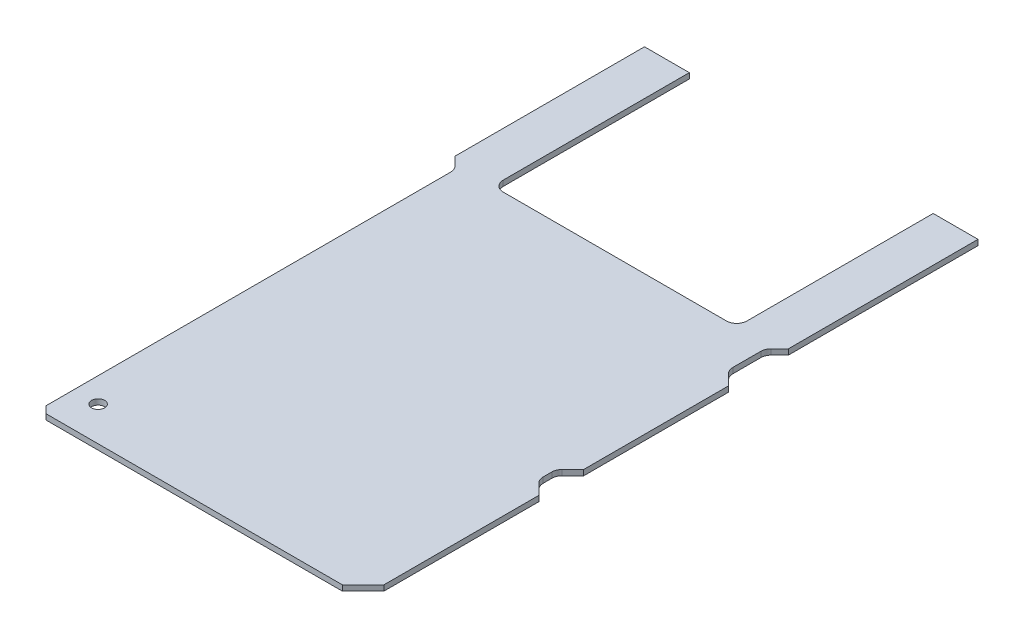
SolidWorks part; units mm, degrees
ref_plane "Front Plane" through (0, 0, 0) normal (0, 0, 1) x (1, 0, 0)
ref_plane "Top Plane" through (0, 0, 0) normal (0, 1, 0) x (1, 0, 0)
ref_plane "Right Plane" through (0, 0, 0) normal (1, 0, 0) x (0, 0, -1)
sketch "Sketch1" plane through (0, 0, 0) normal (0, 1, 0) x (1, 0, 0)
  line L1 (45, -88.5) -> (-45, -88.5)
  line L2 (45, -88.5) -> (45, 88.5)
  line L3 (45, 88.5) -> (-45, 88.5)
  line L4 (-45, -88.5) -> (-45, 88.5)
  line L5 (45, -88.5) -> (-45, 88.5) construction
  line L6 (45, 88.5) -> (-45, -88.5) construction
  point P0 (0, 0)
  dimension "D1" = 90
  dimension "D2" = 177
extrude "Boss-Extrude1" add sketch "Sketch1" along normal blind 1.6
sketch "Sketch5" plane through (0, 0, 0) normal (0, -1, 0) x (1, 0, 0)
  line L0 (45, 88.5) -> (45, -88.5) construction
  line L1 (37.6, -44) -> (37.6, -48)
  line L2 (37.6, -44) -> (22.4, -44)
  line L3 (22.4, -44) -> (22.4, -48)
  line L4 (37.6, -48) -> (22.4, -48)
  line L5 (16.1, -44) -> (16.1, -48)
  line L6 (16.1, -44) -> (0.9, -44)
  line L7 (0.9, -44) -> (0.9, -48)
  line L8 (16.1, -48) -> (0.9, -48)
  line L9 (37.6, -80) -> (37.6, -84)
  line L10 (37.6, -80) -> (22.4, -80)
  line L11 (22.4, -80) -> (22.4, -84)
  line L12 (37.6, -84) -> (22.4, -84)
  line L13 (12.1, -80) -> (12.1, -84)
  line L14 (12.1, -80) -> (-3.1, -80)
  line L15 (-3.1, -80) -> (-3.1, -84)
  line L16 (12.1, -84) -> (-3.1, -84)
  line L17 (2.025, -44.54) -> (14.975, -44.54)
  line L18 (2.025, -44.54) -> (2.025, -47.46)
  line L19 (2.025, -47.46) -> (14.975, -47.46)
  line L20 (14.975, -44.54) -> (14.975, -47.46)
  line L21 (23.525, -44.54) -> (36.475, -44.54)
  line L22 (23.525, -44.54) -> (23.525, -47.46)
  line L23 (23.525, -47.46) -> (36.475, -47.46)
  line L24 (36.475, -44.54) -> (36.475, -47.46)
  line L25 (-1.975, -80.54) -> (10.975, -80.54)
  line L26 (-1.975, -80.54) -> (-1.975, -83.46)
  line L27 (-1.975, -83.46) -> (10.975, -83.46)
  line L28 (10.975, -80.54) -> (10.975, -83.46)
  line L29 (23.525, -80.54) -> (36.475, -80.54)
  line L30 (23.525, -80.54) -> (23.525, -83.46)
  line L31 (23.525, -83.46) -> (36.475, -83.46)
  line L32 (36.475, -80.54) -> (36.475, -83.46)
  line L33 (-22, -41.5) -> (43, -41.5) construction
  line L34 (-22, -41.5) -> (-22, -86.5) construction
  line L35 (-22, -86.5) -> (43, -86.5) construction
  line L36 (43, -41.5) -> (43, -86.5) construction
  line L37 (45, -88.5) -> (-45, -88.5) construction
  point P16 (8.5, -44)
  point P17 (30, -44)
  point P18 (4.5, -84)
  point P19 (30, -84)
  point P25 (37.6, -82)
  point P26 (37.6, -46)
  point P38 (8.5, -44.54)
  point P39 (2.025, -46)
  point P40 (0.9, -46)
  point P41 (30, -44.54)
  point P42 (-1.975, -82)
  point P43 (-3.1, -82)
  point P44 (4.5, -83.46)
  point P45 (30, -83.46)
  dimension "D1" = 15.2
  dimension "D2" = 4
  dimension "D3" = 21.5
  dimension "D4" = 25.5
  dimension "D5" = 2.92
  dimension "D6" = 12.95
  dimension "D7" = 36
  dimension "D8" = 65
  dimension "D9" = 45
  dimension "D10" = 2.5
  dimension "D11" = 5.4
  dimension "D12" = 2
  dimension "D13" = 2
sketch "Sketch7" plane through (0, 0, 0) normal (0, -1, 0) x (1, 0, 0)
  line L0 (-45, -30.1257) -> (-48.3743, -33.5)
  line L1 (-45, -88.5) -> (-48.3743, -88.5)
  line L2 (-45, -88.5) -> (-45, -30.1257)
  line L4 (-48.3743, -88.5) -> (-48.3743, -33.5)
  line L5 (45, -88.5) -> (48.3743, -88.5)
  line L6 (45, -88.5) -> (45, -30.1257)
  line L8 (48.3743, -88.5) -> (48.3743, -33.5)
  line L9 (45, -30.1257) -> (48.3743, -33.5)
  line M9 (-45, 88.5) -> (-45, -88.5)
  line M11 (45, -88.5) -> (45, 88.5)
  dimension "D1" = 3.3743
  dimension "D2" = 55
  dimension "D3" = 45
extrude "Boss-Extrude4" add sketch "Sketch7" against normal up to surface (1.6 mm away) contours L4 L1 L0 M9 | L9 L5 L8 M11 region at (-46.6704, 0, -60.1481) region at (46.6704, 0, -60.1481) up to face at (0, 1.6, 0)
sketch "Sketch8" plane through (0, 1.6, 0) normal (0, 1, 0) x (1, 0, 0)
  line L0 (-30.48, 25.5) -> (30.48, 25.5) construction
  line L2 (48.3743, 88.5) -> (-48.3743, 88.5) construction
  line L3 (31.0783, -41.8002) -> (31.0783, -43.6252) construction
  line L4 (31.0783, -43.6252) -> (29.8783, -43.6252) construction
  line L5 (31.0783, -79.9002) -> (31.0783, -81.7252) construction
  line L6 (31.0783, -81.7252) -> (29.8783, -81.7252) construction
  line L7 (6.9977, -30.7614) -> (6.9977, -16.766)
  line L8 (6.9977, -16.766) -> (-6.9977, -16.766)
  line L9 (-6.9977, -16.766) -> (-6.9977, -30.7614)
  line L10 (-6.9977, -30.7614) -> (6.9977, -30.7614)
  line L11 (6.9977, -30.7614) -> (6.9977, -16.766)
  line L12 (6.9977, -16.766) -> (-6.9977, -16.766)
  line L13 (-6.9977, -16.766) -> (-6.9977, -30.7614)
  line L14 (-6.9977, -30.7614) -> (6.9977, -30.7614)
  line L15 (-11.9253, -30.7614) -> (-11.9253, -16.766)
  line L16 (-11.9253, -16.766) -> (-25.9207, -16.766)
  line L17 (-25.9207, -16.766) -> (-25.9207, -30.7614)
  line L18 (-25.9207, -30.7614) -> (-11.9253, -30.7614)
  line L19 (-11.9253, -30.7614) -> (-11.9253, -16.766)
  line L20 (-11.9253, -16.766) -> (-25.9207, -16.766)
  line L21 (-25.9207, -16.766) -> (-25.9207, -30.7614)
  line L22 (-25.9207, -30.7614) -> (-11.9253, -30.7614)
  line L23 (44.8437, -11.8384) -> (44.8437, 2.157)
  line L24 (44.8437, 2.157) -> (30.8483, 2.157)
  line L25 (30.8483, 2.157) -> (30.8483, -11.8384)
  line L26 (30.8483, -11.8384) -> (44.8437, -11.8384)
  line L27 (44.8437, -11.8384) -> (44.8437, 2.157)
  line L28 (44.8437, 2.157) -> (30.8483, 2.157)
  line L29 (30.8483, 2.157) -> (30.8483, -11.8384)
  line L30 (30.8483, -11.8384) -> (44.8437, -11.8384)
  line L31 (6.9977, -49.6844) -> (6.9977, -35.689)
  line L32 (6.9977, -35.689) -> (-6.9977, -35.689)
  line L33 (-6.9977, -35.689) -> (-6.9977, -49.6844)
  line L34 (-6.9977, -49.6844) -> (6.9977, -49.6844)
  line L35 (6.9977, -49.6844) -> (6.9977, -35.689)
  line L36 (6.9977, -35.689) -> (-6.9977, -35.689)
  line L37 (-6.9977, -35.689) -> (-6.9977, -49.6844)
  line L38 (-6.9977, -49.6844) -> (6.9977, -49.6844)
  line L39 (-11.9253, -49.6844) -> (-11.9253, -35.689)
  line L40 (-11.9253, -35.689) -> (-25.9207, -35.689)
  line L41 (-25.9207, -35.689) -> (-25.9207, -49.6844)
  line L42 (-25.9207, -49.6844) -> (-11.9253, -49.6844)
  line L43 (-11.9253, -49.6844) -> (-11.9253, -35.689)
  line L44 (-11.9253, -35.689) -> (-25.9207, -35.689)
  line L45 (-25.9207, -35.689) -> (-25.9207, -49.6844)
  line L46 (-25.9207, -49.6844) -> (-11.9253, -49.6844)
  line L47 (25.9207, -30.7614) -> (25.9207, -16.766)
  line L48 (25.9207, -16.766) -> (11.9253, -16.766)
  line L49 (11.9253, -16.766) -> (11.9253, -30.7614)
  line L50 (11.9253, -30.7614) -> (25.9207, -30.7614)
  line L51 (25.9207, -30.7614) -> (25.9207, -16.766)
  line L52 (25.9207, -16.766) -> (11.9253, -16.766)
  line L53 (11.9253, -16.766) -> (11.9253, -30.7614)
  line L54 (11.9253, -30.7614) -> (25.9207, -30.7614)
  line L55 (6.9977, -68.6074) -> (6.9977, -54.612)
  line L56 (6.9977, -54.612) -> (-6.9977, -54.612)
  line L57 (-6.9977, -54.612) -> (-6.9977, -68.6074)
  line L58 (-6.9977, -68.6074) -> (6.9977, -68.6074)
  line L59 (6.9977, -68.6074) -> (6.9977, -54.612)
  line L60 (6.9977, -54.612) -> (-6.9977, -54.612)
  line L61 (-6.9977, -54.612) -> (-6.9977, -68.6074)
  line L62 (-6.9977, -68.6074) -> (6.9977, -68.6074)
  line L63 (-11.9253, -68.6074) -> (-11.9253, -54.612)
  line L64 (-11.9253, -54.612) -> (-25.9207, -54.612)
  line L65 (-25.9207, -54.612) -> (-25.9207, -68.6074)
  line L66 (-25.9207, -68.6074) -> (-11.9253, -68.6074)
  line L67 (-11.9253, -68.6074) -> (-11.9253, -54.612)
  line L68 (-11.9253, -54.612) -> (-25.9207, -54.612)
  line L69 (-25.9207, -54.612) -> (-25.9207, -68.6074)
  line L70 (-25.9207, -68.6074) -> (-11.9253, -68.6074)
  line L71 (25.9207, -49.6844) -> (25.9207, -35.689)
  line L72 (25.9207, -35.689) -> (11.9253, -35.689)
  line L73 (11.9253, -35.689) -> (11.9253, -49.6844)
  line L74 (11.9253, -49.6844) -> (25.9207, -49.6844)
  line L75 (25.9207, -49.6844) -> (25.9207, -35.689)
  line L76 (25.9207, -35.689) -> (11.9253, -35.689)
  line L77 (11.9253, -35.689) -> (11.9253, -49.6844)
  line L78 (11.9253, -49.6844) -> (25.9207, -49.6844)
  line L79 (25.9207, -68.6074) -> (25.9207, -54.612)
  line L80 (25.9207, -54.612) -> (11.9253, -54.612)
  line L81 (11.9253, -54.612) -> (11.9253, -68.6074)
  line L82 (11.9253, -68.6074) -> (25.9207, -68.6074)
  line L83 (25.9207, -68.6074) -> (25.9207, -54.612)
  line L84 (25.9207, -54.612) -> (11.9253, -54.612)
  line L85 (11.9253, -54.612) -> (11.9253, -68.6074)
  line L86 (11.9253, -68.6074) -> (25.9207, -68.6074)
  line L87 (-30.8483, -30.7614) -> (-30.8483, -16.766)
  line L88 (-30.8483, -16.766) -> (-44.8437, -16.766)
  line L89 (-44.8437, -16.766) -> (-44.8437, -30.7614)
  line L90 (-44.8437, -30.7614) -> (-30.8483, -30.7614)
  line L91 (-30.8483, -30.7614) -> (-30.8483, -16.766)
  line L92 (-30.8483, -16.766) -> (-44.8437, -16.766)
  line L93 (-44.8437, -16.766) -> (-44.8437, -30.7614)
  line L94 (-44.8437, -30.7614) -> (-30.8483, -30.7614)
  line L95 (-30.8483, -11.8384) -> (-30.8483, 2.157)
  line L96 (-30.8483, 2.157) -> (-44.8437, 2.157)
  line L97 (-44.8437, 2.157) -> (-44.8437, -11.8384)
  line L98 (-44.8437, -11.8384) -> (-30.8483, -11.8384)
  line L99 (-30.8483, -11.8384) -> (-30.8483, 2.157)
  line L100 (-30.8483, 2.157) -> (-44.8437, 2.157)
  line L101 (-44.8437, 2.157) -> (-44.8437, -11.8384)
  line L102 (-44.8437, -11.8384) -> (-30.8483, -11.8384)
  line L103 (25.9207, -87.5304) -> (25.9207, -73.535)
  line L104 (25.9207, -73.535) -> (11.9253, -73.535)
  line L105 (11.9253, -73.535) -> (11.9253, -87.5304)
  line L106 (11.9253, -87.5304) -> (25.9207, -87.5304)
  line L107 (25.9207, -87.5304) -> (25.9207, -73.535)
  line L108 (25.9207, -73.535) -> (11.9253, -73.535)
  line L109 (11.9253, -73.535) -> (11.9253, -87.5304)
  line L110 (11.9253, -87.5304) -> (25.9207, -87.5304)
  line L111 (-30.8483, -87.5304) -> (-30.8483, -73.535)
  line L112 (-30.8483, -73.535) -> (-44.8437, -73.535)
  line L113 (-44.8437, -73.535) -> (-44.8437, -87.5304)
  line L114 (-44.8437, -87.5304) -> (-30.8483, -87.5304)
  line L115 (-30.8483, -87.5304) -> (-30.8483, -73.535)
  line L116 (-30.8483, -73.535) -> (-44.8437, -73.535)
  line L117 (-44.8437, -73.535) -> (-44.8437, -87.5304)
  line L118 (-44.8437, -87.5304) -> (-30.8483, -87.5304)
  line L119 (-30.8483, -68.6074) -> (-30.8483, -54.612)
  line L120 (-30.8483, -54.612) -> (-44.8437, -54.612)
  line L121 (-44.8437, -54.612) -> (-44.8437, -68.6074)
  line L122 (-44.8437, -68.6074) -> (-30.8483, -68.6074)
  line L123 (-30.8483, -68.6074) -> (-30.8483, -54.612)
  line L124 (-30.8483, -54.612) -> (-44.8437, -54.612)
  line L125 (-44.8437, -54.612) -> (-44.8437, -68.6074)
  line L126 (-44.8437, -68.6074) -> (-30.8483, -68.6074)
  line L127 (-30.8483, -49.6844) -> (-30.8483, -35.689)
  line L128 (-30.8483, -35.689) -> (-44.8437, -35.689)
  line L129 (-44.8437, -35.689) -> (-44.8437, -49.6844)
  line L130 (-44.8437, -49.6844) -> (-30.8483, -49.6844)
  line L131 (-30.8483, -49.6844) -> (-30.8483, -35.689)
  line L132 (-30.8483, -35.689) -> (-44.8437, -35.689)
  line L133 (-44.8437, -35.689) -> (-44.8437, -49.6844)
  line L134 (-44.8437, -49.6844) -> (-30.8483, -49.6844)
  line L135 (45.0596, 90.786) -> (-45.0596, 90.786)
  line L136 (-45.0596, 90.786) -> (-45.0596, 30.08)
  line L137 (-45.0596, 30.08) -> (45.0596, 30.08)
  line L138 (45.0596, 30.08) -> (45.0596, 90.786)
  line L139 (45.0596, 90.786) -> (-45.0596, 90.786)
  line L140 (-45.0596, 90.786) -> (-45.0596, 30.08)
  line L141 (-45.0596, 30.08) -> (45.0596, 30.08)
  line L142 (45.0596, 30.08) -> (45.0596, 90.786)
  line L143 (52.5, 98.836) -> (-52.5, 98.836)
  line L144 (52.5, -92.8744) -> (52.5, 98.836)
  line L145 (-52.5, -92.8744) -> (52.5, -92.8744)
  line L146 (-52.5, 98.836) -> (-52.5, -92.8744)
  line L147 (52.5, 98.836) -> (-52.5, 98.836)
  line L148 (52.5, -92.8744) -> (52.5, 98.836)
  line L149 (-52.5, -92.8744) -> (52.5, -92.8744)
  line L150 (-52.5, 98.836) -> (-52.5, -92.8744)
  line L151 (-18.0365, -73.765) -> (-19.8615, -73.765) construction
  line L152 (-19.8615, -73.765) -> (-19.8615, -72.565) construction
  line L153 (31.8783, -41.8002) -> (31.0783, -41.8002) construction
  line L154 (31.8783, -79.9002) -> (31.0783, -79.9002) construction
  line L155 (-18.0365, -74.565) -> (-18.0365, -73.765) construction
  line L156 (31.8783, -40.2252) -> (31.8783, -41.8002) construction
  line L157 (31.8783, -78.3252) -> (31.8783, -79.9002) construction
  line L158 (-16.4615, -74.565) -> (-18.0365, -74.565) construction
  line L159 (-6.9977, 7.0846) -> (-6.9977, 21.08) construction
  line L160 (6.9977, 21.08) -> (-6.9977, 21.08) construction
  line L161 (31.0783, -48.4502) -> (37.3483, -48.4502) construction
  line L162 (37.3483, -48.4502) -> (40.1483, -48.4502) construction
  line L163 (31.0783, -86.5502) -> (37.3483, -86.5502) construction
  line L164 (37.3483, -86.5502) -> (40.1483, -86.5502) construction
  line L165 (-24.6865, -73.765) -> (-24.6865, -80.035) construction
  line L166 (-24.6865, -80.035) -> (-24.6865, -82.835) construction
  line L167 (6.9977, 7.0846) -> (-6.9977, 7.0846) construction
  line L168 (43.3783, -48.4502) -> (43.3783, -41.8002) construction
  line L169 (43.3783, -41.8002) -> (42.5783, -41.8002) construction
  line L170 (43.3783, -86.5502) -> (43.3783, -79.9002) construction
  line L171 (43.3783, -79.9002) -> (42.5783, -79.9002) construction
  line L172 (-24.6865, -86.065) -> (-18.0365, -86.065) construction
  line L173 (-18.0365, -86.065) -> (-18.0365, -85.265) construction
  line L174 (6.9977, 7.0846) -> (6.9977, 21.08) construction
  line L175 (40.1483, -48.4502) -> (43.3783, -48.4502) construction
  line L176 (40.1483, -86.5502) -> (43.3783, -86.5502) construction
  line L177 (-24.6865, -82.835) -> (-24.6865, -86.065) construction
  line L178 (-25.9207, 7.0846) -> (-25.9207, 21.08) construction
  line L179 (-11.9253, 21.08) -> (-25.9207, 21.08) construction
  line L180 (29.8783, -43.6252) -> (29.8783, -46.6252) construction
  line L181 (29.8783, -81.7252) -> (29.8783, -84.7252) construction
  line L182 (-19.8615, -72.565) -> (-22.8615, -72.565) construction
  line L183 (-11.9253, 7.0846) -> (-25.9207, 7.0846) construction
  line L184 (31.0783, -46.6252) -> (31.0783, -48.4502) construction
  line L185 (31.0783, -84.7252) -> (31.0783, -86.5502) construction
  line L186 (-22.8615, -73.765) -> (-24.6865, -73.765) construction
  line L187 (-30.8483, 7.0846) -> (-44.8437, 7.0846) construction
  line L188 (-30.8483, 7.0846) -> (-30.8483, 21.08) construction
  line L189 (-30.8483, 21.08) -> (-44.8437, 21.08) construction
  line L190 (-44.8437, 7.0846) -> (-44.8437, 21.08) construction
  line L191 (30.8483, -26.2252) -> (30.8483, -40.2252) construction
  line L192 (30.8483, -40.2252) -> (31.8783, -40.2252) construction
  line L193 (30.8483, -64.3252) -> (30.8483, -78.3252) construction
  line L194 (30.8483, -78.3252) -> (31.8783, -78.3252) construction
  line L195 (-2.4615, -73.535) -> (-16.4615, -73.535) construction
  line L196 (-16.4615, -73.535) -> (-16.4615, -74.565) construction
  line L197 (-11.9253, 7.0846) -> (-11.9253, 21.08) construction
  line L198 (29.8783, -46.6252) -> (31.0783, -46.6252) construction
  line L199 (29.8783, -84.7252) -> (31.0783, -84.7252) construction
  line L200 (-22.8615, -72.565) -> (-22.8615, -73.765) construction
  line L201 (-6.9977, -11.8384) -> (-6.9977, 2.157) construction
  line L202 (6.9977, 2.157) -> (-6.9977, 2.157) construction
  line L203 (31.0783, -19.8252) -> (31.0783, -18.0002) construction
  line L204 (29.8783, -19.8252) -> (31.0783, -19.8252) construction
  line L205 (31.0783, -57.9252) -> (31.0783, -56.1002) construction
  line L206 (29.8783, -57.9252) -> (31.0783, -57.9252) construction
  line L207 (3.9385, -73.765) -> (5.7635, -73.765) construction
  line L208 (3.9385, -72.565) -> (3.9385, -73.765) construction
  line L209 (6.9977, -11.8384) -> (-6.9977, -11.8384) construction
  line L210 (31.0783, -22.8252) -> (29.8783, -22.8252) construction
  line L211 (31.0783, -24.6502) -> (31.0783, -22.8252) construction
  line L212 (31.0783, -60.9252) -> (29.8783, -60.9252) construction
  line L213 (31.0783, -62.7502) -> (31.0783, -60.9252) construction
  line L214 (0.9385, -73.765) -> (0.9385, -72.565) construction
  line L215 (-0.8865, -73.765) -> (0.9385, -73.765) construction
  line L216 (6.9977, -11.8384) -> (6.9977, 2.157) construction
  line L217 (29.8783, -22.8252) -> (29.8783, -19.8252) construction
  line L218 (29.8783, -60.9252) -> (29.8783, -57.9252) construction
  line L219 (0.9385, -72.565) -> (3.9385, -72.565) construction
  line L220 (-25.9207, -11.8384) -> (-25.9207, 2.157) construction
  line L221 (-11.9253, 2.157) -> (-25.9207, 2.157) construction
  line L222 (43.3783, -18.0002) -> (43.3783, -24.6502) construction
  line L223 (40.1483, -18.0002) -> (43.3783, -18.0002) construction
  line L224 (43.3783, -56.1002) -> (43.3783, -62.7502) construction
  line L225 (40.1483, -56.1002) -> (43.3783, -56.1002) construction
  line L226 (5.7635, -86.065) -> (-0.8865, -86.065) construction
  line L227 (5.7635, -82.835) -> (5.7635, -86.065) construction
  line L228 (-11.9253, -11.8384) -> (-25.9207, -11.8384) construction
  line L229 (31.0783, -18.0002) -> (37.3483, -18.0002) construction
  line L230 (31.0783, -56.1002) -> (37.3483, -56.1002) construction
  line L231 (5.7635, -73.765) -> (5.7635, -80.035) construction
  line L232 (-11.9253, -11.8384) -> (-11.9253, 2.157) construction
  line L233 (37.3483, -18.0002) -> (40.1483, -18.0002) construction
  line L234 (37.3483, -56.1002) -> (40.1483, -56.1002) construction
  line L235 (5.7635, -80.035) -> (5.7635, -82.835) construction
  line L236 (30.8483, 7.0846) -> (30.8483, 21.08) construction
  line L237 (44.8437, 21.08) -> (30.8483, 21.08) construction
  line L238 (44.8483, -40.2252) -> (44.8483, -26.2252) construction
  line L239 (42.5783, -26.2252) -> (44.8483, -26.2252) construction
  line L240 (44.8483, -78.3252) -> (44.8483, -64.3252) construction
  line L241 (42.5783, -64.3252) -> (44.8483, -64.3252) construction
  line L242 (-16.4615, -87.535) -> (-2.4615, -87.535) construction
  line L243 (-2.4615, -85.265) -> (-2.4615, -87.535) construction
  line L244 (44.8437, 7.0846) -> (30.8483, 7.0846) construction
  line L245 (43.3783, -24.6502) -> (42.5783, -24.6502) construction
  line L246 (43.3783, -62.7502) -> (42.5783, -62.7502) construction
  line L247 (-0.8865, -86.065) -> (-0.8865, -85.265) construction
  line L248 (44.8437, 7.0846) -> (44.8437, 21.08) construction
  line L249 (42.5783, -24.6502) -> (42.5783, -26.2252) construction
  line L250 (42.5783, -62.7502) -> (42.5783, -64.3252) construction
  line L251 (-0.8865, -85.265) -> (-2.4615, -85.265) construction
  line L252 (25.9207, 7.0846) -> (11.9253, 7.0846) construction
  line L253 (11.9253, 7.0846) -> (11.9253, 21.08) construction
  line L254 (25.9207, 21.08) -> (11.9253, 21.08) construction
  line L255 (42.5783, -41.8002) -> (42.5783, -40.2252) construction
  line L256 (42.5783, -79.9002) -> (42.5783, -78.3252) construction
  line L257 (-18.0365, -85.265) -> (-16.4615, -85.265) construction
  line L258 (25.9207, 7.0846) -> (25.9207, 21.08) construction
  line L259 (42.5783, -40.2252) -> (44.8483, -40.2252) construction
  line L260 (42.5783, -78.3252) -> (44.8483, -78.3252) construction
  line L261 (-16.4615, -85.265) -> (-16.4615, -87.535) construction
  line L262 (11.9253, -11.8384) -> (11.9253, 2.157) construction
  line L263 (25.9207, 2.157) -> (11.9253, 2.157) construction
  line L264 (31.8783, -24.6502) -> (31.0783, -24.6502) construction
  line L265 (31.8783, -62.7502) -> (31.0783, -62.7502) construction
  line L266 (-0.8865, -74.565) -> (-0.8865, -73.765) construction
  line L267 (25.9207, -11.8384) -> (11.9253, -11.8384) construction
  line L268 (30.8483, -26.2252) -> (31.8783, -26.2252) construction
  line L269 (30.8483, -64.3252) -> (31.8783, -64.3252) construction
  line L270 (-2.4615, -73.535) -> (-2.4615, -74.565) construction
  line L271 (25.9207, -11.8384) -> (25.9207, 2.157) construction
  line L272 (31.8783, -26.2252) -> (31.8783, -24.6502) construction
  line L273 (31.8783, -64.3252) -> (31.8783, -62.7502) construction
  line L274 (-2.4615, -74.565) -> (-0.8865, -74.565) construction
  line L275 (-24.6865, -86.065) -> (-25.1945, -86.065) construction
  line L276 (-25.1945, -86.065) -> (-25.1945, -73.765) construction
  line L277 (-25.1945, -73.765) -> (-24.6865, -73.765) construction
  line L278 (31.0783, -48.4502) -> (31.0783, -48.9582) construction
  line L279 (31.0783, -48.9582) -> (43.3783, -48.9582) construction
  line L280 (43.3783, -48.9582) -> (43.3783, -48.4502) construction
  line L281 (31.0783, -56.1002) -> (31.0783, -55.5922) construction
  line L282 (31.0783, -55.5922) -> (43.3783, -55.5922) construction
  line L283 (43.3783, -55.5922) -> (43.3783, -56.1002) construction
  line L284 (31.0783, -86.5502) -> (31.0783, -87.0582) construction
  line L285 (31.0783, -87.0582) -> (43.3783, -87.0582) construction
  line L286 (43.3783, -87.0582) -> (43.3783, -86.5502) construction
  line L287 (5.7635, -73.765) -> (6.2715, -73.765) construction
  line L288 (6.2715, -73.765) -> (6.2715, -86.065) construction
  line L289 (6.2715, -86.065) -> (5.7635, -86.065) construction
  line L290 (31.0783, -18.0002) -> (31.0783, -17.4922) construction
  line L291 (31.0783, -17.4922) -> (43.3783, -17.4922) construction
  line L292 (43.3783, -17.4922) -> (43.3783, -18.0002) construction
  line L293 (31.0783, -41.8002) -> (31.0783, -43.6252)
  line L294 (31.0783, -43.6252) -> (29.8783, -43.6252)
  line L295 (31.0783, -79.9002) -> (31.0783, -81.7252)
  line L296 (31.0783, -81.7252) -> (29.8783, -81.7252)
  line L297 (-18.0365, -73.765) -> (-19.8615, -73.765)
  line L298 (-19.8615, -73.765) -> (-19.8615, -72.565)
  line L299 (31.8783, -41.8002) -> (31.0783, -41.8002)
  line L300 (31.8783, -79.9002) -> (31.0783, -79.9002)
  line L301 (-18.0365, -74.565) -> (-18.0365, -73.765)
  line L302 (31.8783, -40.2252) -> (31.8783, -41.8002)
  line L303 (31.8783, -78.3252) -> (31.8783, -79.9002)
  line L304 (-16.4615, -74.565) -> (-18.0365, -74.565)
  line L305 (-6.9977, 7.0846) -> (-6.9977, 21.08)
  line L306 (6.9977, 21.08) -> (-6.9977, 21.08)
  line L307 (31.0783, -48.4502) -> (37.3483, -48.4502)
  line L308 (37.3483, -48.4502) -> (40.1483, -48.4502)
  line L309 (31.0783, -86.5502) -> (37.3483, -86.5502)
  line L310 (37.3483, -86.5502) -> (40.1483, -86.5502)
  line L311 (-24.6865, -73.765) -> (-24.6865, -80.035)
  line L312 (-24.6865, -80.035) -> (-24.6865, -82.835)
  line L313 (6.9977, 7.0846) -> (-6.9977, 7.0846)
  line L314 (43.3783, -48.4502) -> (43.3783, -41.8002)
  line L315 (43.3783, -41.8002) -> (42.5783, -41.8002)
  line L316 (43.3783, -86.5502) -> (43.3783, -79.9002)
  line L317 (43.3783, -79.9002) -> (42.5783, -79.9002)
  line L318 (-24.6865, -86.065) -> (-18.0365, -86.065)
  line L319 (-18.0365, -86.065) -> (-18.0365, -85.265)
  line L320 (6.9977, 7.0846) -> (6.9977, 21.08)
  line L321 (40.1483, -48.4502) -> (43.3783, -48.4502)
  line L322 (40.1483, -86.5502) -> (43.3783, -86.5502)
  line L323 (-24.6865, -82.835) -> (-24.6865, -86.065)
  line L324 (-25.9207, 7.0846) -> (-25.9207, 21.08)
  line L325 (-11.9253, 21.08) -> (-25.9207, 21.08)
  line L326 (29.8783, -43.6252) -> (29.8783, -46.6252)
  line L327 (29.8783, -81.7252) -> (29.8783, -84.7252)
  line L328 (-19.8615, -72.565) -> (-22.8615, -72.565)
  line L329 (-11.9253, 7.0846) -> (-25.9207, 7.0846)
  line L330 (31.0783, -46.6252) -> (31.0783, -48.4502)
  line L331 (31.0783, -84.7252) -> (31.0783, -86.5502)
  line L332 (-22.8615, -73.765) -> (-24.6865, -73.765)
  line L333 (-30.8483, 7.0846) -> (-44.8437, 7.0846)
  line L334 (-30.8483, 7.0846) -> (-30.8483, 21.08)
  line L335 (-30.8483, 21.08) -> (-44.8437, 21.08)
  line L336 (-44.8437, 7.0846) -> (-44.8437, 21.08)
  line L337 (30.8483, -26.2252) -> (30.8483, -40.2252)
  line L338 (30.8483, -40.2252) -> (31.8783, -40.2252)
  line L339 (30.8483, -64.3252) -> (30.8483, -78.3252)
  line L340 (30.8483, -78.3252) -> (31.8783, -78.3252)
  line L341 (-2.4615, -73.535) -> (-16.4615, -73.535)
  line L342 (-16.4615, -73.535) -> (-16.4615, -74.565)
  line L343 (-11.9253, 7.0846) -> (-11.9253, 21.08)
  line L344 (29.8783, -46.6252) -> (31.0783, -46.6252)
  line L345 (29.8783, -84.7252) -> (31.0783, -84.7252)
  line L346 (-22.8615, -72.565) -> (-22.8615, -73.765)
  line L347 (-6.9977, -11.8384) -> (-6.9977, 2.157)
  line L348 (6.9977, 2.157) -> (-6.9977, 2.157)
  line L349 (31.0783, -19.8252) -> (31.0783, -18.0002)
  line L350 (29.8783, -19.8252) -> (31.0783, -19.8252)
  line L351 (31.0783, -57.9252) -> (31.0783, -56.1002)
  line L352 (29.8783, -57.9252) -> (31.0783, -57.9252)
  line L353 (3.9385, -73.765) -> (5.7635, -73.765)
  line L354 (3.9385, -72.565) -> (3.9385, -73.765)
  line L355 (6.9977, -11.8384) -> (-6.9977, -11.8384)
  line L356 (31.0783, -22.8252) -> (29.8783, -22.8252)
  line L357 (31.0783, -24.6502) -> (31.0783, -22.8252)
  line L358 (31.0783, -60.9252) -> (29.8783, -60.9252)
  line L359 (31.0783, -62.7502) -> (31.0783, -60.9252)
  line L360 (0.9385, -73.765) -> (0.9385, -72.565)
  line L361 (-0.8865, -73.765) -> (0.9385, -73.765)
  line L362 (6.9977, -11.8384) -> (6.9977, 2.157)
  line L363 (29.8783, -22.8252) -> (29.8783, -19.8252)
  line L364 (29.8783, -60.9252) -> (29.8783, -57.9252)
  line L365 (0.9385, -72.565) -> (3.9385, -72.565)
  line L366 (-25.9207, -11.8384) -> (-25.9207, 2.157)
  line L367 (-11.9253, 2.157) -> (-25.9207, 2.157)
  line L368 (43.3783, -18.0002) -> (43.3783, -24.6502)
  line L369 (40.1483, -18.0002) -> (43.3783, -18.0002)
  line L370 (43.3783, -56.1002) -> (43.3783, -62.7502)
  line L371 (40.1483, -56.1002) -> (43.3783, -56.1002)
  line L372 (5.7635, -86.065) -> (-0.8865, -86.065)
  line L373 (5.7635, -82.835) -> (5.7635, -86.065)
  line L374 (-11.9253, -11.8384) -> (-25.9207, -11.8384)
  line L375 (31.0783, -18.0002) -> (37.3483, -18.0002)
  line L376 (31.0783, -56.1002) -> (37.3483, -56.1002)
  line L377 (5.7635, -73.765) -> (5.7635, -80.035)
  line L378 (-11.9253, -11.8384) -> (-11.9253, 2.157)
  line L379 (37.3483, -18.0002) -> (40.1483, -18.0002)
  line L380 (37.3483, -56.1002) -> (40.1483, -56.1002)
  line L381 (5.7635, -80.035) -> (5.7635, -82.835)
  line L382 (30.8483, 7.0846) -> (30.8483, 21.08)
  line L383 (44.8437, 21.08) -> (30.8483, 21.08)
  line L384 (44.8483, -40.2252) -> (44.8483, -26.2252)
  line L385 (42.5783, -26.2252) -> (44.8483, -26.2252)
  line L386 (44.8483, -78.3252) -> (44.8483, -64.3252)
  line L387 (42.5783, -64.3252) -> (44.8483, -64.3252)
  line L388 (-16.4615, -87.535) -> (-2.4615, -87.535)
  line L389 (-2.4615, -85.265) -> (-2.4615, -87.535)
  line L390 (44.8437, 7.0846) -> (30.8483, 7.0846)
  line L391 (43.3783, -24.6502) -> (42.5783, -24.6502)
  line L392 (43.3783, -62.7502) -> (42.5783, -62.7502)
  line L393 (-0.8865, -86.065) -> (-0.8865, -85.265)
  line L394 (44.8437, 7.0846) -> (44.8437, 21.08)
  line L395 (42.5783, -24.6502) -> (42.5783, -26.2252)
  line L396 (42.5783, -62.7502) -> (42.5783, -64.3252)
  line L397 (-0.8865, -85.265) -> (-2.4615, -85.265)
  line L398 (25.9207, 7.0846) -> (11.9253, 7.0846)
  line L399 (11.9253, 7.0846) -> (11.9253, 21.08)
  line L400 (25.9207, 21.08) -> (11.9253, 21.08)
  line L401 (42.5783, -41.8002) -> (42.5783, -40.2252)
  line L402 (42.5783, -79.9002) -> (42.5783, -78.3252)
  line L403 (-18.0365, -85.265) -> (-16.4615, -85.265)
  line L404 (25.9207, 7.0846) -> (25.9207, 21.08)
  line L405 (42.5783, -40.2252) -> (44.8483, -40.2252)
  line L406 (42.5783, -78.3252) -> (44.8483, -78.3252)
  line L407 (-16.4615, -85.265) -> (-16.4615, -87.535)
  line L408 (11.9253, -11.8384) -> (11.9253, 2.157)
  line L409 (25.9207, 2.157) -> (11.9253, 2.157)
  line L410 (31.8783, -24.6502) -> (31.0783, -24.6502)
  line L411 (31.8783, -62.7502) -> (31.0783, -62.7502)
  line L412 (-0.8865, -74.565) -> (-0.8865, -73.765)
  line L413 (25.9207, -11.8384) -> (11.9253, -11.8384)
  line L414 (30.8483, -26.2252) -> (31.8783, -26.2252)
  line L415 (30.8483, -64.3252) -> (31.8783, -64.3252)
  line L416 (-2.4615, -73.535) -> (-2.4615, -74.565)
  line L417 (25.9207, -11.8384) -> (25.9207, 2.157)
  line L418 (31.8783, -26.2252) -> (31.8783, -24.6502)
  line L419 (31.8783, -64.3252) -> (31.8783, -62.7502)
  line L420 (-2.4615, -74.565) -> (-0.8865, -74.565)
  line L421 (-24.6865, -86.065) -> (-25.1945, -86.065)
  line L422 (-25.1945, -86.065) -> (-25.1945, -73.765)
  line L423 (-25.1945, -73.765) -> (-24.6865, -73.765)
  line L424 (31.0783, -48.4502) -> (31.0783, -48.9582)
  line L425 (31.0783, -48.9582) -> (43.3783, -48.9582)
  line L426 (43.3783, -48.9582) -> (43.3783, -48.4502)
  line L427 (31.0783, -56.1002) -> (31.0783, -55.5922)
  line L428 (31.0783, -55.5922) -> (43.3783, -55.5922)
  line L429 (43.3783, -55.5922) -> (43.3783, -56.1002)
  line L430 (31.0783, -86.5502) -> (31.0783, -87.0582)
  line L431 (31.0783, -87.0582) -> (43.3783, -87.0582)
  line L432 (43.3783, -87.0582) -> (43.3783, -86.5502)
  line L433 (5.7635, -73.765) -> (6.2715, -73.765)
  line L434 (6.2715, -73.765) -> (6.2715, -86.065)
  line L435 (6.2715, -86.065) -> (5.7635, -86.065)
  line L436 (31.0783, -18.0002) -> (31.0783, -17.4922)
  line L437 (31.0783, -17.4922) -> (43.3783, -17.4922)
  line L438 (43.3783, -17.4922) -> (43.3783, -18.0002)
  circle A0 centre (-45.8343, 84.563) radius 0.4318 construction
  circle A1 centre (-45.8343, 84.563) radius 0.4318
  circle A2 centre (45.8343, 84.563) radius 0.4318 construction
  circle A3 centre (45.8343, 84.563) radius 0.4318
  circle A8 centre (-45.8343, 82.023) radius 0.4318
  circle A9 centre (45.8343, 82.023) radius 0.4318
  circle A10 centre (-45.8343, 79.483) radius 0.4318
  circle A11 centre (45.8343, 79.483) radius 0.4318
  circle A12 centre (-45.8343, 76.943) radius 0.4318
  circle A13 centre (45.8343, 76.943) radius 0.4318
  circle A14 centre (-45.8343, 74.403) radius 0.4318
  circle A15 centre (45.8343, 74.403) radius 0.4318
  circle A16 centre (-45.8343, 71.863) radius 0.4318
  circle A17 centre (45.8343, 71.863) radius 0.4318
  circle A18 centre (-45.8343, 69.323) radius 0.4318
  circle A19 centre (45.8343, 69.323) radius 0.4318
  circle A20 centre (-45.8343, 66.783) radius 0.4318
  circle A21 centre (45.8343, 66.783) radius 0.4318
  circle A22 centre (-45.8343, 64.243) radius 0.4318
  circle A23 centre (45.8343, 64.243) radius 0.4318
  circle A24 centre (-45.8343, 61.703) radius 0.4318
  circle A25 centre (45.8343, 61.703) radius 0.4318
  circle A26 centre (-45.8343, 59.163) radius 0.4318
  circle A27 centre (45.8343, 59.163) radius 0.4318
  circle A28 centre (-45.8343, 56.623) radius 0.4318
  circle A29 centre (45.8343, 56.623) radius 0.4318
  circle A30 centre (-45.8343, 54.083) radius 0.4318
  circle A31 centre (45.8343, 54.083) radius 0.4318
  circle A32 centre (-45.8343, 51.543) radius 0.4318
  circle A33 centre (45.8343, 51.543) radius 0.4318
  circle A34 centre (-45.8343, 49.003) radius 0.4318
  circle A35 centre (45.8343, 49.003) radius 0.4318
  circle A36 centre (-45.8343, 46.463) radius 0.4318
  circle A37 centre (45.8343, 46.463) radius 0.4318
  circle A38 centre (-45.8343, 43.923) radius 0.4318
  circle A39 centre (45.8343, 43.923) radius 0.4318
  circle A40 centre (-45.8343, 41.383) radius 0.4318
  circle A41 centre (45.8343, 41.383) radius 0.4318
  circle A42 centre (-45.8343, 38.843) radius 0.4318
  circle A43 centre (45.8343, 38.843) radius 0.4318
  circle A44 centre (-45.8343, 36.303) radius 0.4318
  circle A45 centre (45.8343, 36.303) radius 0.4318
  arc A47 (-45.0596, 32.62) -> (-42.5196, 30.08) centre (-42.5196, 32.62) ccw construction
  circle A48 centre (-37.846, -80.5327) radius 1.9
  circle A49 centre (-30.48, 25.5) radius 0.4318
  circle A50 centre (-27.94, 25.5) radius 0.4318
  circle A51 centre (-25.4, 25.5) radius 0.4318
  circle A52 centre (-22.86, 25.5) radius 0.4318
  circle A53 centre (-20.32, 25.5) radius 0.4318
  circle A54 centre (-17.78, 25.5) radius 0.4318
  circle A55 centre (-15.24, 25.5) radius 0.4318
  circle A56 centre (-12.7, 25.5) radius 0.4318
  circle A57 centre (-10.16, 25.5) radius 0.4318
  circle A58 centre (-7.62, 25.5) radius 0.4318
  circle A59 centre (-5.08, 25.5) radius 0.4318
  circle A60 centre (-2.54, 25.5) radius 0.4318
  circle A61 centre (0, 25.5) radius 0.4318
  circle A62 centre (2.54, 25.5) radius 0.4318
  circle A63 centre (5.08, 25.5) radius 0.4318
  circle A64 centre (7.62, 25.5) radius 0.4318
  circle A65 centre (10.16, 25.5) radius 0.4318
  circle A66 centre (12.7, 25.5) radius 0.4318
  circle A67 centre (15.24, 25.5) radius 0.4318
  circle A68 centre (17.78, 25.5) radius 0.4318
  circle A69 centre (20.32, 25.5) radius 0.4318
  circle A70 centre (22.86, 25.5) radius 0.4318
  circle A71 centre (25.4, 25.5) radius 0.4318
  circle A72 centre (27.94, 25.5) radius 0.4318
  circle A73 centre (30.48, 25.5) radius 0.4318
  circle A74 centre (-37.846, -80.5327) radius 2
  circle A75 centre (-37.846, -80.5327) radius 2
  arc A76 (42.5196, 30.08) -> (45.0596, 32.62) centre (42.5196, 32.62) ccw construction
  arc A77 (45.0596, 88.246) -> (42.5196, 90.786) centre (42.5196, 88.246) ccw construction
  arc A78 (-42.5196, 90.786) -> (-45.0596, 88.246) centre (-42.5196, 88.246) ccw construction
  arc A79 (-45.0596, 32.62) -> (-42.5196, 30.08) centre (-42.5196, 32.62) ccw
  arc A80 (42.5196, 30.08) -> (45.0596, 32.62) centre (42.5196, 32.62) ccw
  arc A81 (45.0596, 88.246) -> (42.5196, 90.786) centre (42.5196, 88.246) ccw
  arc A82 (-42.5196, 90.786) -> (-45.0596, 88.246) centre (-42.5196, 88.246) ccw
  dimension "D3" = 3.8
  dimension "D2" = 2.54
  dimension "D5" = 2.54
  dimension "D6" = 63
  dimension "D1" = 20
  dimension "D7" = 0
  dimension "D8" = 0
  dimension "D9" = 0
  dimension "D10" = 0
  dimension "D11" = 0
  dimension "D12" = 0
  dimension "D13" = 0
  dimension "D14" = 0
  dimension "D15" = 0
  dimension "D16" = 0
  dimension "D17" = 0
  dimension "D18" = 0
  dimension "D19" = 0
  dimension "D20" = 0
  dimension "D21" = 0
  dimension "D22" = 0
  dimension "D23" = 0
  dimension "D24" = 0
  dimension "D25" = 0
  dimension "D4" = 25
extrude "Cut-Extrude1" cut sketch "Sketch8" against normal through all contours A48 region at (-37.846, 1.6, 80.5327)
extrude "Cut-Extrude2" [suppressed] cut sketch "Sketch5" against normal through all
sketch "w" plane through (0, 1.6, 0) normal (0, 1, 0) x (1, 0, 0)
  line L0 (45, -88.5) -> (49, -84.5)
  line L1 (45, -88.5) -> (45, 30.1257) construction
  line L2 (49, -84.5) -> (49, -39.5)
  line L3 (49, -39.5) -> (45, -35.5)
  line L4 (45, -30.5) -> (49, -26.5)
  line L5 (49, -26.5) -> (49, 15.5)
  line L6 (49, 15.5) -> (45, 19.5)
  line L7 (45, 19.5) -> (45, -30.5)
  line L8 (45, -35.5) -> (45, -88.5)
  line L9 (-45, -88.5) -> (45, -88.5) construction
  line L10 (-45, -88.5) -> (-43, -90.5)
  line L11 (-43, -90.5) -> (43, -90.5)
  line L12 (43, -90.5) -> (45, -88.5)
  line L13 (-45, -88.5) -> (45, -88.5)
  line M54 (-45, -88.5) -> (45, -88.5)
  line M55 (45, -88.5) -> (45, 30.1257)
  dimension "D1" = 4
  dimension "D2" = 45
  dimension "D3" = 53
  dimension "D4" = 50
  dimension "D5" = 5
  dimension "D6" = 2
extrude "Boss-Extrude5" add sketch "w" against normal up to surface (1.6 mm away) contours L11 L12 L10 M54 | L2 L3 L0 M55 | L5 L6 L4 M55 region at (46.9456, 1.6, 62) region at (46.942, 1.6, 5.5) region at (0, 1.6, 89.4924) up to face at (-37.846, 0, 82.4327)
sketch "Sketch9" plane through (0, 0, 0) normal (0, -1, 0) x (1, 0, 0)
  line L0 (48.3743, -88.5) -> (-48.3743, -88.5) construction
  line L1 (-35.3743, -88.5) -> (35.3743, -88.5)
  line L2 (-35.3743, -88.5) -> (-35.3743, -31.5)
  line L3 (-35.3743, -31.5) -> (35.3743, -31.5)
  line L4 (35.3743, -88.5) -> (35.3743, -31.5)
  line L5 (48.3743, -88.5) -> (48.3743, -33.5) construction
  line L6 (-48.3743, -88.5) -> (-48.3743, -33.5) construction
  dimension "D1" = 13
  dimension "D2" = 13
  dimension "D3" = 57
extrude "Cut-Extrude3" cut sketch "Sketch9" against normal through all
fillet "Fillet1" radius 3 7 edges at (45, 0.8, -30.1257) (-45, 0.8, -30.1257) (45, 0.8, -19.5) (45, 0.8, 30.5) (45, 0.8, 35.5) (-35.3743, 0.8, -31.5) (35.3743, 0.8, -31.5)
